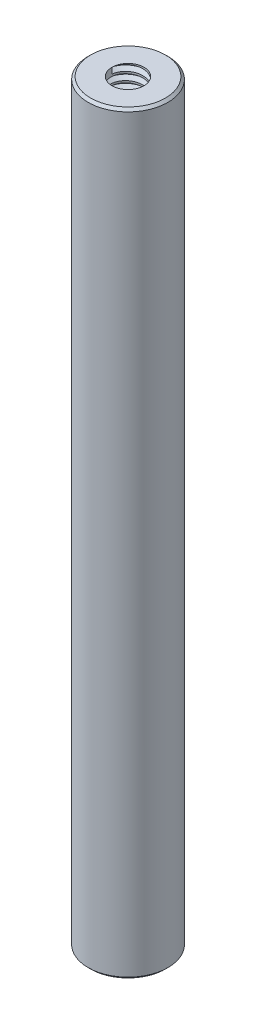
SolidWorks part; units mm, degrees
material "6061-T6 (SS)"
ref_plane "Alzado" through (0, 0, 0) normal (0, 0, 1) x (1, 0, 0)
ref_plane "Planta" through (0, 0, 0) normal (0, 1, 0) x (1, 0, 0)
ref_plane "Vista lateral" through (0, 0, 0) normal (1, 0, 0) x (0, 0, -1)
sketch "Croquis2" plane through (0, 0, 0) normal (0, 1, 0) x (1, 0, 0)
  circle A0 centre (0, 0) radius 6.35
  dimension "D1" = 12.7
extrude "Saliente-Extruir1" add sketch "Croquis2" along normal mid plane 120.0813
chamfer "Chaflán1" distance 0.3969 angle 45 2 edges at (0, -60.0407, 6.35) (0, 60.0407, 6.35)
sketch "Croquis3" plane through (0, 0, 0) normal (0, 1, 0) x (1, 0, 0)
  circle A0 centre (0, 0) radius 2.5527
  dimension "D1" = 5.1054
extrude "Tap Hole 1" cut sketch "Croquis3" against normal blind 19.05 from surface starting at face at (0, 60.0407, 5.9531)
extrude "Tap Hole 2" cut sketch "Croquis3<2>" along normal blind 19.05 from surface starting at face at (0, -60.0407, 5.9531)
sketch "Croquis3<2>" plane through (0, 0, 0) normal (0, 1, 0) x (1, 0, 0) same geometry as "Croquis3"
sketch "Croquis4" plane through (0, 0, 0) normal (0, 1, 0) x (1, 0, 0)
  circle A0 centre (0, 0) radius 3.2639
  dimension "D1" = 6.5278
extrude "Clearance Hole" [suppressed] cut sketch "Croquis4" against normal through all both and the other way through all
thread "Rosca1" pitch 1.27 method cut profile "Perfil de rosca1" start angle 0, offset 0, length 0, pitch 1.27, diameter 5.1054
ref_plane "Plano1" through (-2.5527, 60.0407, 0) normal (0, 0, 1) x (-1, 0, 0)
sketch "Perfil de rosca1" plane through (-2.5527, 60.0407, 0) normal (0, 0, 1) x (-1, 0, 0)
  line L0 (0, 0) -> (0, 1.27) construction
  line L1 (0, 0) -> (0.6874, 0.3969)
  line L2 (0.6874, 0.3969) -> (0.6874, 0.5556)
  line L3 (0.6874, 0.5556) -> (0, 0.9525)
  line L4 (0.6874, 0.4762) -> (0, 0.4762) construction
  line L11 (0, 0) -> (0, 0.9525)
  point P2 (0, 0)
  dimension "Pitch" = 1.27
  dimension "Profile_Angle" = 60
  dimension "Profile_Land" = 0.1588
  dimension "Profile_Height" = 0.6874
thread "Rosca2" pitch 1.27 method cut profile "Perfil de rosca2" start angle 0, offset 0, length 0, pitch 1.27, diameter 5.1054
ref_plane "Plano2" through (2.5527, -60.0407, 0) normal (0, 0, 1) x (1, 0, 0)
sketch "Perfil de rosca2" plane through (2.5527, -60.0407, 0) normal (0, 0, 1) x (1, 0, 0)
  line L0 (0, 0) -> (0, 1.27) construction
  line L1 (0, 0) -> (0.6874, 0.3969)
  line L2 (0.6874, 0.3969) -> (0.6874, 0.5556)
  line L3 (0.6874, 0.5556) -> (0, 0.9525)
  line L4 (0.6874, 0.4762) -> (0, 0.4762) construction
  line L11 (0, 0) -> (0, 0.9525)
  point P2 (0, 0)
  dimension "Pitch" = 1.27
  dimension "Profile_Angle" = 60
  dimension "Profile_Land" = 0.1588
  dimension "Profile_Height" = 0.6874
equation "\"OD\"= 0.5pulgadas"
equation "\"Largo\"= 4.72761024pulgadas"
equation "\"Tap Hole\"= IIF ( \"OD\" = 0.375pulgadas , 0.1590pulgadas , 0.201pulgadas )"
equation "\"Spacer Hole\"= IIF ( \"OD\" = 0.375pulgadas , 0.196pulgadas , 0.257pulgadas )"
equation "\"D1@Croquis2\"=\"OD\""
equation "\"D1@Saliente-Extruir1\"=\"Largo\""
equation "\"D1@Croquis3\"=\"Tap Hole\""
equation "\"D1@Croquis4\"=\"Spacer Hole\""
